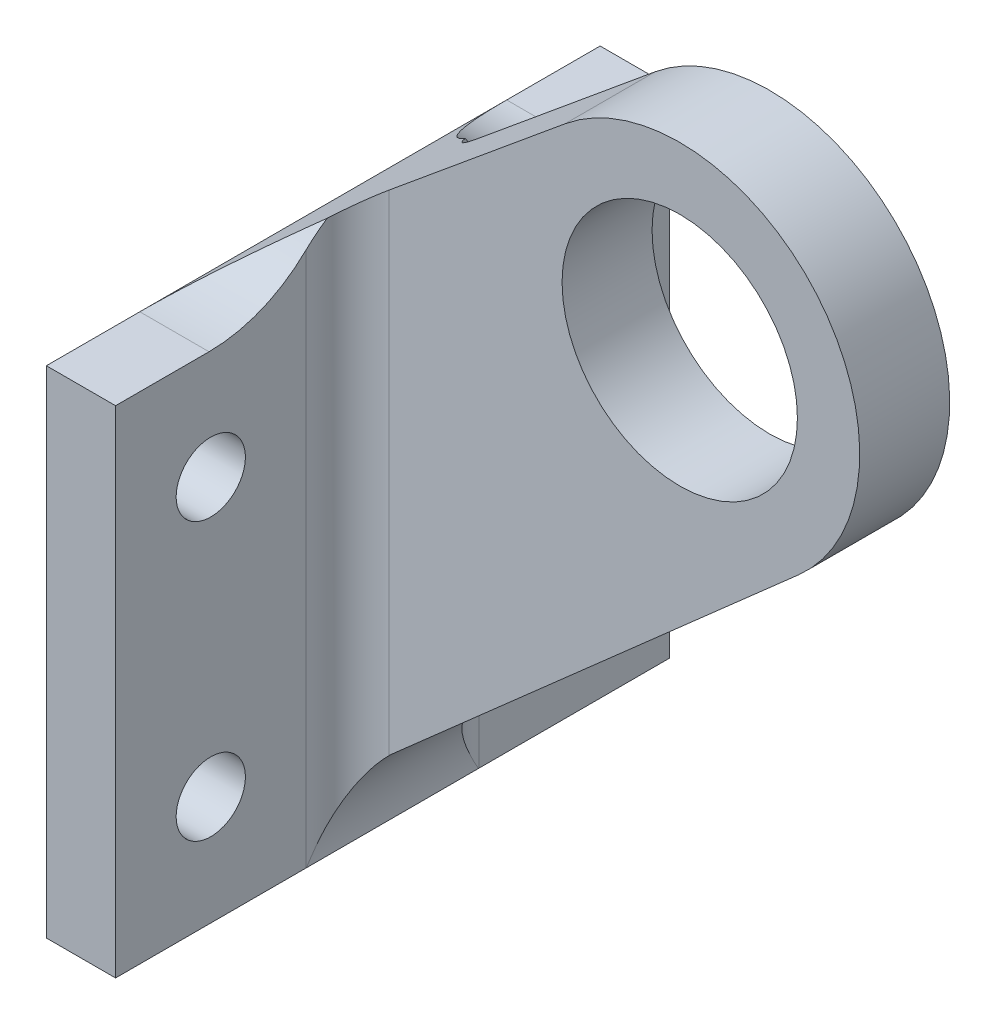
SolidWorks part; units mm, degrees
ref_plane "Front Plane" through (0, 0, 0) normal (0, 0, 1) x (1, 0, 0)
ref_plane "Top Plane" through (0, 0, 0) normal (0, 1, 0) x (1, 0, 0)
ref_plane "Right Plane" through (0, 0, 0) normal (1, 0, 0) x (0, 0, -1)
sketch "Sketch1" plane through (0, 0, 0) normal (0, 0, 1) x (1, 0, 0)
  line L0 (0, 0) -> (39, 35) construction
  line L1 (39, 35) -> (39, 0) construction
  line L2 (39, 0) -> (0, 0) construction
  line L3 (0, 0) -> (0, 20) construction
  line L4 (0, 20) -> (39, 35) construction
  line L5 (10, 0) -> (10, -7.9) construction
  line L6 (0, 20) -> (10, 20) construction
  line L7 (10, 20) -> (10, 27.9) construction
  line L8 (10, 27.9) -> (10, -7.9)
  line L9 (10, 27.9) -> (30.719, 45.0212)
  line L10 (10, -7.9) -> (47.5974, 25.2489)
  circle A0 centre (39, 35) radius 13 construction
  circle A1 centre (39, 35) radius 13
  circle A2 centre (39, 35) radius 8.5
  point P3 (10, 0)
  dimension "D5" = 26
  dimension "D9" = 17
  dimension "D1" = 20
  dimension "D2" = 10
  dimension "D3" = 39
  dimension "D4" = 35
  dimension "D6" = 7.9
  dimension "D7" = 7.9
  dimension "D8" = 10
extrude "Boss-Extrude1" add sketch "Sketch1" along normal mid plane 6.5 contours A1 | A1 L9 L8 L10 region at (21.2888, 17.3689, 0) region at (44.3817, 46.4286, 0)
sketch "Sketch3" plane through (10, 0, 0) normal (-1, 0, 0) x (0, 0, 1)
  line L0 (3.25, -7.9) -> (-3.25, -7.9) construction
  line L1 (-20, 27.9) -> (20, 27.9)
  line L2 (-20, 27.9) -> (-20, -7.9)
  line L3 (-20, -7.9) -> (20, -7.9)
  line L4 (20, 27.9) -> (20, -7.9)
  line L5 (3.25, 27.9) -> (-3.25, 27.9) construction
  point P8 (0, 0)
  point P9 (0, -7.9)
  dimension "D1" = 40
extrude "Boss-Extrude3" add sketch "Sketch3" against normal blind 5
fillet "Fillet1" radius 10 3 edges at (15, -3.4916, 0) (12.5, 27.9, -3.25) (12.5, 27.9, 3.25)
fillet "Fillet2" radius 3 2 edges at (15, 12.0659, -3.25) (15, 12.0659, 3.25)
sketch "Sketch5" plane through (10, 0, 0) normal (-1, 0, 0) x (0, 0, 1)
  line L0 (0, 27.9) -> (0, -7.9) construction
  line L1 (13.25, 27.9) -> (-13.25, 27.9) construction
  line L2 (20, -7.9) -> (-20, -7.9) construction
  line L3 (3.25, 37.1442) -> (3.25, -7.9) construction
  line L4 (13.125, -7.9) -> (13.125, 0) construction
  line L5 (13.125, 0) -> (13.125, 20) construction
  line L6 (3.25, 34.5108) -> (3.25, 45.0212) construction
  line L7 (6.25, 27.9) -> (6.25, -7.9) construction
  line L8 (6.25, -7.9) -> (20, -7.9) construction
  circle A0 centre (13.125, 0) radius 2.5
  circle A1 centre (13.125, 20) radius 2.5
  point P18 (13.125, -7.9)
  dimension "D3" = 5
  dimension "D4" = 5
  dimension "D1" = 7.9
  dimension "D2" = 20
  dimension "D5" = 3
extrude "Cut-Extrude1" cut sketch "Sketch5" against normal through all
mirror "Mirror1" about plane through (0, 0, 0) normal (0, 0, 1) of "Cut-Extrude1"
